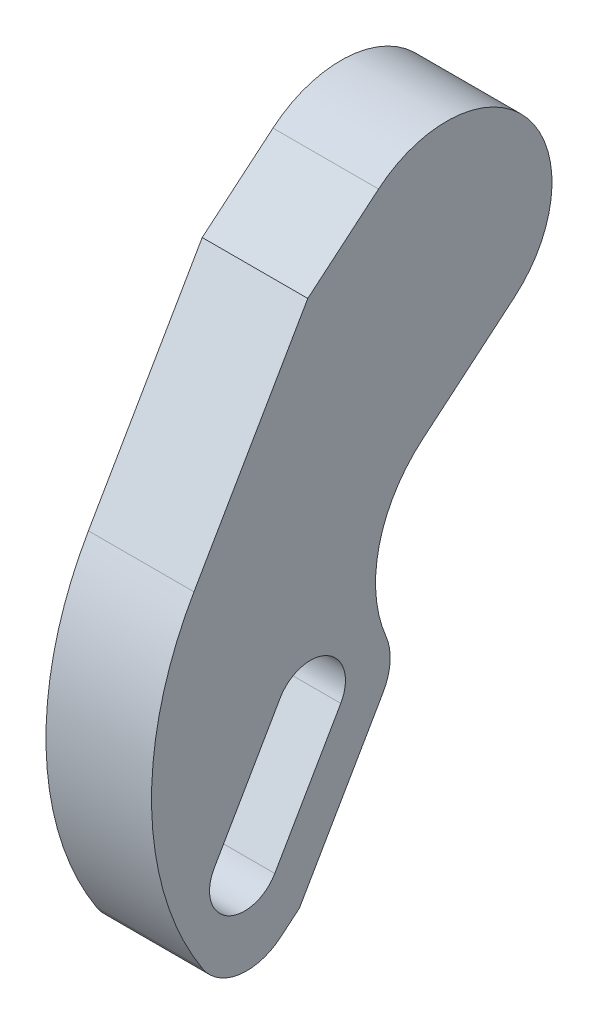
SolidWorks part; units mm, degrees
ref_plane "Front Plane" through (0, 0, 0) normal (0, 0, 1) x (1, 0, 0)
ref_plane "Top Plane" through (0, 0, 0) normal (0, 1, 0) x (1, 0, 0)
ref_plane "Right Plane" through (0, 0, 0) normal (1, 0, 0) x (0, 0, -1)
sketch "Sketch5" plane through (0, 0, 0) normal (1, 0, 0) x (0, 0, -1)
  circle A0 centre (0, 0) radius 4
  dimension "D1" = 8
extrude "Boss-Extrude2" add sketch "Sketch5" along normal blind 4
sketch "Sketch6" plane through (0, 0, 0) normal (1, 0, 0) x (0, 0, -1)
  line L0 (-2.5712, 3.0642) -> (2.5712, -3.0642)
  line L1 (-2.5712, 3.0642) -> (-17.509, -9.4702)
  line L2 (2.5712, -3.0642) -> (-12.3667, -15.5985)
  line L3 (-17.509, -9.4702) -> (-12.3667, -15.5985)
  line L4 (0, 0) -> (-15.0686, 0) construction
  point P0 (0, 0)
  dimension "D1" = 8
  dimension "D2" = 19.5
  dimension "D3" = 40
extrude "Boss-Extrude3" add sketch "Sketch6" along normal blind 4
sketch "Sketch7" plane through (0, 0, 0) normal (-1, 0, 0) x (0, 0, 1)
  circle A0 centre (0, 0) radius 2.6
  dimension "D1" = 5.2
extrude "Cut-Extrude3" cut sketch "Sketch7" against normal blind 2.5
sketch "Sketch8" plane through (2.5, 0, 0) normal (-1, 0, 0) x (0, 0, 1)
  line L0 (1.6, -0.75) -> (-1.6, -0.75)
  line L1 (1.6, -0.75) -> (1.6, 0.75)
  line L2 (-1.6, -0.75) -> (-1.6, 0.75)
  line L3 (1.6, 0.75) -> (0.65, 0.75)
  line L5 (0.65, 0.75) -> (0.65, 1.25)
  line L6 (-0.65, 0.75) -> (-0.65, 1.25)
  line L7 (0.65, 1.25) -> (-0.65, 1.25)
  line L8 (-0.65, 0.75) -> (-1.6, 0.75)
  line L9 (1.6, 0) -> (-1.6, 0) construction
  line L10 (-9.3611, 0) -> (9.3611, 0) construction
  point P10 (0, 0)
  point P17 (0, 0)
  dimension "D1" = 1.5
  dimension "D2" = 3.2
  dimension "D3" = 1.3
  dimension "D4" = 0.5
  dimension "D5" = 0
extrude "Boss-Extrude4" add sketch "Sketch8" along normal blind 2.5
fillet "Fillet1" radius 0.3 4 edges at (1.25, -0.75, 1.6) (1.25, 0.75, 1.6) (1.25, -0.75, -1.6) (1.25, 0.75, -1.6)
sketch "Sketch9" plane through (0, -3.0642, -2.5712) normal (0, -0.766, -0.6428) x (1, 0, 0)
  line L0 (4, 19.5) -> (4, 0) construction
  line L1 (0, 19.5) -> (4, 19.5)
  line L2 (0, 19.5) -> (0, 9.5)
  line L3 (0, 9.5) -> (4, 9.5)
  line L4 (4, 19.5) -> (4, 9.5)
  dimension "D1" = 10
extrude "Boss-Extrude5" add sketch "Sketch9" along normal blind 7
sketch "Sketch10" plane through (4, 0, 0) normal (1, 0, 0) x (0, 0, -1)
  line L0 (-5.15, -12.4349) -> (-7.65, -16.7651) construction
  line L1 (-4.0025, -13.0974) -> (-6.5025, -17.4276)
  line L2 (-6.2975, -11.7724) -> (-8.7975, -16.1026)
  line L3 (15.7034, 0) -> (-15.7034, 0) construction
  arc A0 (-4.0025, -13.0974) -> (-6.2975, -11.7724) centre (-5.15, -12.4349) ccw
  arc A1 (-8.7975, -16.1026) -> (-6.5025, -17.4276) centre (-7.65, -16.7651) ccw
  point P2 (-6.4, -14.6)
  point P11 (0, 0)
  dimension "D1" = 60
  dimension "D2" = 2.65
  dimension "D3" = 5
  dimension "D4" = 14.6
  dimension "D5" = 6.4
extrude "Cut-Extrude4" cut sketch "Sketch10" against normal up to next
chamfer "Chamfer1" distance 16 angle 20 1 edges at (2, -9.4702, 17.509) first distance on face at (2, -3.203, 10.0401)
chamfer "Chamfer2" distance 7 angle 20 1 edges at (2, -14.533, 0.2068) first distance on face at (2, -17.7469, 4.037)
fillet "Fillet5" radius 5 1 edges at (2, -9.1707, 4.7063)
fillet "Fillet6" radius 12 1 edges at (2, -13.9313, 13.7657)
fillet "Fillet7" radius 2 2 edges at (2, -12.5812, 1.8444) (2, -20.9608, 7.8672)
